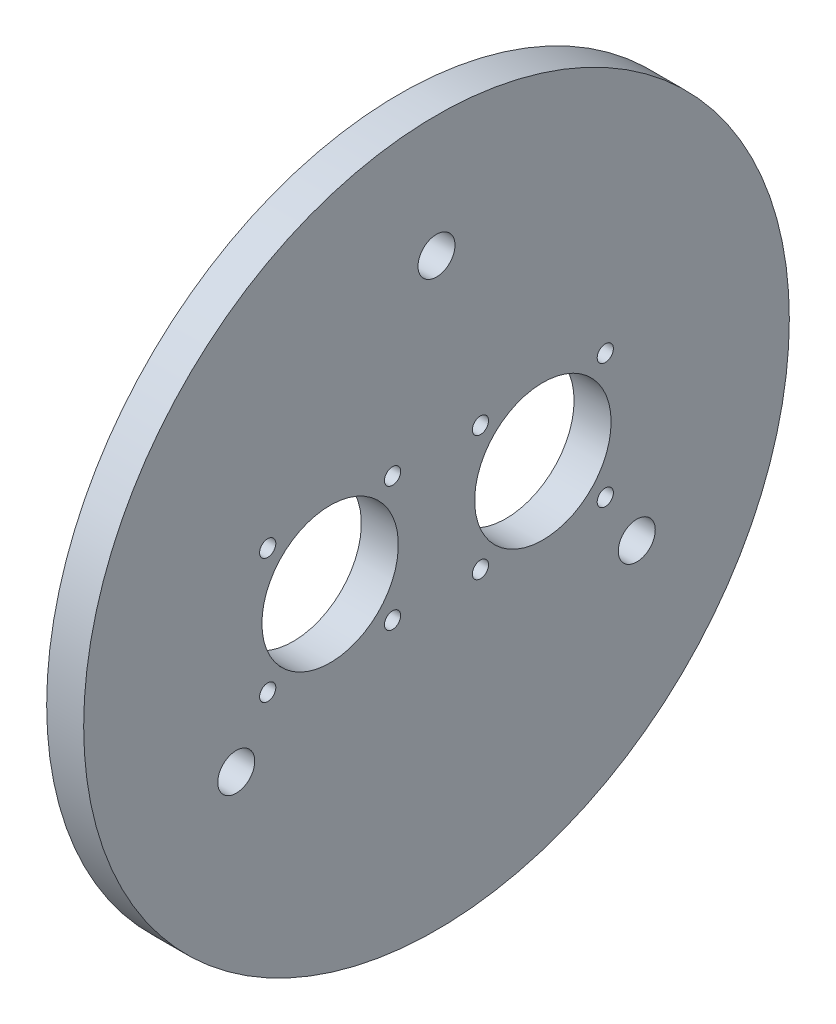
SolidWorks part; units mm, degrees
ref_plane "Front Plane" through (0, 0, 0) normal (0, 0, 1) x (1, 0, 0)
ref_plane "Top Plane" through (0, 0, 0) normal (0, 1, 0) x (1, 0, 0)
ref_plane "Right Plane" through (0, 0, 0) normal (1, 0, 0) x (0, 0, -1)
sketch "Sketch1" plane through (0, 0, 0) normal (1, 0, 0) x (0, 0, -1)
  line L0 (0, -76.29) -> (0, 76.29) construction
  line L1 (-76.29, 0) -> (76.29, 0) construction
  line L2 (23, 0) -> (36.4969, 13.4969) construction
  circle A0 centre (0, 0) radius 76.29
  circle A1 centre (0, 50) radius 4
  circle A2 centre (43.3013, -25) radius 4
  circle A3 centre (-43.3013, -25) radius 4
  circle A4 centre (23, 0) radius 14.75
  circle A5 centre (-23, 0) radius 14.75
  circle A6 centre (36.4969, 13.4969) radius 1.75
  circle A7 centre (36.4969, -13.4969) radius 1.75
  circle A8 centre (9.5031, -13.4969) radius 1.75
  circle A9 centre (9.5031, 13.4969) radius 1.75
  circle A10 centre (-36.4969, -13.4969) radius 1.75
  circle A11 centre (-9.5031, -13.4969) radius 1.75
  circle A12 centre (-9.5031, 13.4969) radius 1.75
  circle A13 centre (-36.4969, 13.4969) radius 1.75
  point P12 (0, 0)
  point P29 (23, 0)
  dimension "D1" = 152.58
  dimension "D2" = 8
  dimension "D5" = 29.5
  dimension "D7" = 3.5
  dimension "D3" = 50
  dimension "D4" = 3
  dimension "D6" = 23
  dimension "D8" = 19.0875
  dimension "D10" = 45
  dimension "D9" = 4
extrude "Boss-Extrude1" add sketch "Sketch1" along normal blind 8
